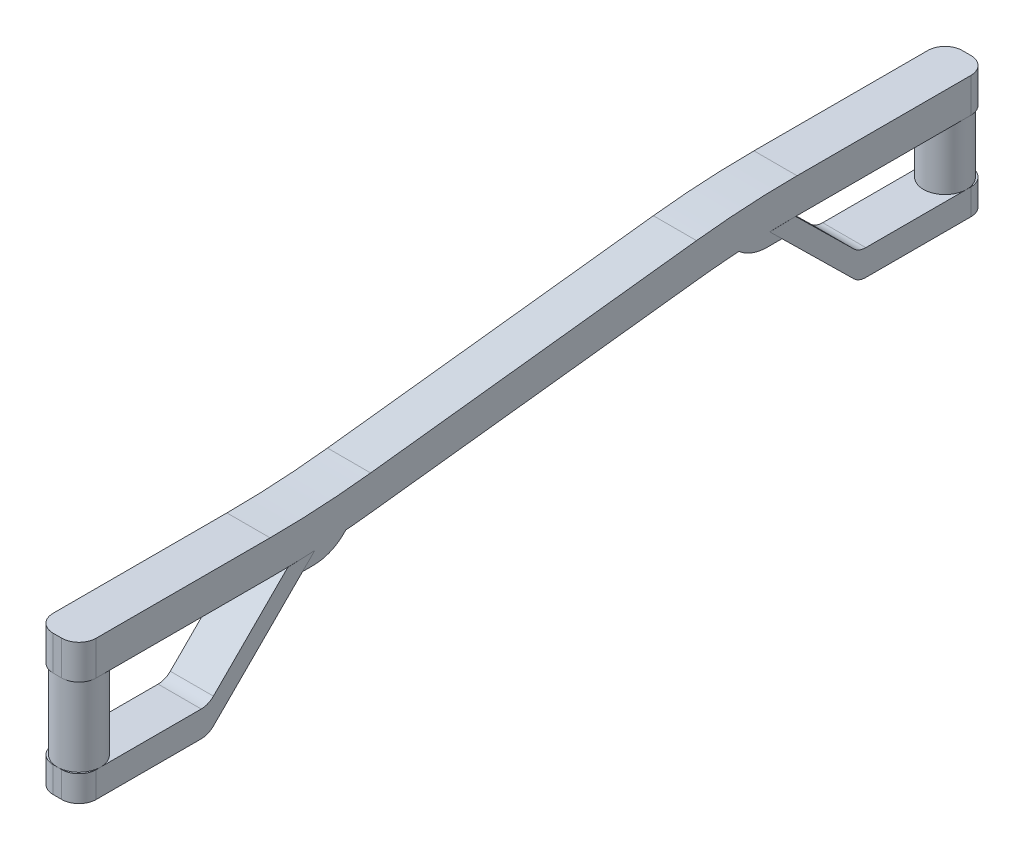
SolidWorks part; units mm, degrees
note: The reader was unsure of these and kept them because the rebuilt part matched: shared geometry of "Sketch1<3>", "Sketch1<4>", "Sketch4<4>".
other "End Rod cap 2"
other "End Rod Cap"
other "Long Connecting Rod"
material "PLA 100% Infill"
ref_plane "Front Plane" through (0, 0, 0) normal (0, 0, 1) x (1, 0, 0)
ref_plane "Top Plane" through (0, 0, 0) normal (0, 1, 0) x (1, 0, 0)
ref_plane "Right Plane" through (0, 0, 0) normal (1, 0, 0) x (0, 0, -1)
sketch "Sketch1" plane through (0, 0, 0) normal (0, 1, 0) x (1, 0, 0)
  line L1 (0, 0) -> (-5, 0)
  line L2 (0, 0) -> (0, -105.4)
  line L3 (0, -105.4) -> (-5, -105.4)
  line L4 (-5, 0) -> (-5, -105.4)
  circle A0 centre (-2.5, -2.5) radius 2.5
  circle A1 centre (-2.5, -102.9) radius 2.5
  dimension "D1" = 100.4
  dimension "D2" = 5
extrude "Boss-Extrude1" add sketch "Sketch1" along normal blind 4 contours L4 L3 L2 L1
extrude "Boss-Extrude2" add sketch "Sketch1<3>" against normal blind 15 contours A1
sketch "Sketch1<3>" plane through (0, 0, 0) normal (0, 1, 0) x (1, 0, 0) same geometry as "Sketch1"
extrude "Boss-Extrude3" add sketch "Sketch1<4>" against normal blind 7.2 contours A0
sketch "Sketch1<4>" plane through (0, 0, 0) normal (0, 1, 0) x (1, 0, 0) same geometry as "Sketch1"
fillet "Fillet1" radius 1 2 edges at (0, 2, 105.4) (-5, 2, 105.4)
ref_plane "Plane1" through (0, -17.2, 0) normal (0, -1, 0) x (-1, 0, 0)
sketch "Sketch2" plane through (0, -15, 0) normal (0, -1, 0) x (1, 0, 0)
  line L3 (-1.8333, 104.0547) -> (-1.8333, 101.7453)
  line L4 (-1.8333, 101.7453) -> (-3.8333, 102.9)
  line L6 (-3.8333, 102.9) -> (-1.8333, 104.0547)
  line L7 (-3.8333, 102.9) -> (-1.8333, 102.9) construction
  line L8 (-2.5, 105.4) -> (-2.5, 100.4) construction
  line L9 (-2.8333, 103.4774) -> (-1.8333, 101.7453) construction
  arc A0 (-5, 102.9) -> (0, 102.9) centre (-2.5, 102.9) ccw construction
  point P11 (-2.5, 102.9)
  dimension "D1" = 2
extrude "Cut-Extrude1" cut sketch "Sketch2" against normal blind 7
sketch "Sketch3" plane through (0, -7.2, 0) normal (0, -1, 0) x (-1, 0, 0)
  line L0 (3.1667, -1.3453) -> (3.1667, -3.6547)
  line L1 (3.1667, -3.6547) -> (1.1667, -2.5)
  line L2 (1.1667, -2.5) -> (3.1667, -1.3453)
  line L3 (1.1667, -2.5) -> (3.1667, -2.5) construction
  line L4 (2.5, 0) -> (2.5, -5) construction
  line L5 (2.1667, -1.9226) -> (3.1667, -3.6547) construction
  arc A1 (0, -2.5) -> (5, -2.5) centre (2.5, -2.5) ccw construction
  point P8 (2.5, -2.5)
  dimension "D1" = 2
extrude "Cut-Extrude2" cut sketch "Sketch3" against normal blind 7
sketch "Sketch4" plane through (-5, 0, 0) normal (-1, 0, 0) x (0, 0, 1)
  line L0 (105.4, -1.8) -> (105.4, -5.8)
  line L1 (105.4, -15) -> (105.4, 0) construction
  line L2 (105.4, -5.8) -> (77.4, -5.8)
  line L3 (77.4, -5.8) -> (28, 0)
  line L4 (2.5, 0) -> (102.9, 0) construction
  line L5 (105.4, -1.8) -> (77.4, -1.8)
  line L7 (77.4, -1.8) -> (77.4, -5.8) construction
  line L9 (0, 4) -> (104.4, 4) construction
  line L10 (28, 4) -> (28, 0)
  line L11 (28, 4) -> (105.4, 4)
  line L12 (105.4, 4) -> (105.4, -1.8)
  line L13 (28, 4) -> (77.4, -1.8)
  dimension "D1" = 4
  dimension "D2" = 28
  dimension "D3" = 5.8
  dimension "28" = 28
extrude "Boss-Extrude4" add sketch "Sketch4" against normal up to surface (5 mm away) up to face at (0, 1.3333, 52.3667)
extrude "Cut-Extrude3" cut sketch "Sketch4<4>" against normal up to surface (5 mm away)
sketch "Sketch4<4>" plane through (-5, 0, 0) normal (-1, 0, 0) x (0, 0, 1) same geometry as "Sketch4"
fillet "Fillet2" radius 100 4 edges at (-2.5, 4, 28) (-2.5, -1.8, 77.4) (-2.5, -5.8, 77.4) (-2.5, 0, 28)
sketch "Sketch5" plane through (0, 0, 0) normal (1, 0, 0) x (0, 0, -1)
  line L0 (-90.4, -15) -> (-81.2, -5.8)
  line L1 (-105.4, -15) -> (-90.4, -15)
  line L2 (-105.4, -15) -> (-105.4, -18)
  line L3 (-105.4, -18) -> (-90.4, -18)
  line L4 (-90.4, -15) -> (-90.4, -18) construction
  line L5 (-102.9, -5.8) -> (-83.2504, -5.8) construction
  line L6 (-90.4, -18) -> (-78.0655, -5.6655)
  line L7 (-5, -7.2) -> (0, -7.2) construction
  line L8 (0, -7.2) -> (-15, -7.2)
  line L9 (0, -7.2) -> (0, -10.2)
  line L10 (0, -10.2) -> (-15, -10.2)
  line L11 (-15, -7.2) -> (-15, -10.2) construction
  line L12 (-15, -7.2) -> (-22.3212, -0.0001)
  line L13 (-15, -10.2) -> (-25.3208, -0.0503)
  line L14 (0, -7.2) -> (0, 0) construction
  line L15 (-22.3212, -0.0001) -> (-25.3208, -0.0503)
  line L17 (-81.2, -5.8) -> (-78.0655, -5.6655)
  arc A0 (-83.2504, -5.8) -> (-71.5896, -5.1178) centre (-83.2504, 94.2) ccw construction
  arc A1 (-22.1496, 0) -> (-33.8104, -0.6822) centre (-22.1496, -100) ccw construction
  dimension "D1" = 45
  dimension "D3" = 3
  dimension "D4" = 15
extrude "Boss-Extrude6" add sketch "Sketch5" against normal up to surface (5 mm away) separate body up to face at (-5, -1.1857, 52.7)
sketch "Sketch6" plane through (0, 0, 0) normal (1, 0, 0) x (0, 0, -1)
  line L0 (-78.0655, -5.6655) -> (-79.4797, -7.0797)
  line L1 (-52.7, 1.1) -> (-52.7, -2.9) construction
  line L2 (-33.8104, 3.3178) -> (-71.5896, -1.1178) construction
  line L3 (-71.5896, -5.1178) -> (-33.8104, -0.6822) construction
  line L5 (-28.8948, -0.2277) -> (-28.8948, -1.4526)
  line L7 (-90.4, -18) -> (-78.0655, -5.6655) construction
  line L8 (-79.4797, -7.0797) -> (-74.4797, -7.0797)
  line L9 (-74.4797, -7.0797) -> (-74.4797, -5.4146)
  line L12 (-78.0655, -5.6655) -> (-74.4797, -5.4146)
  line L16 (-28.8948, -1.4526) -> (-23.8948, -1.4526)
  line L17 (-25.3208, -0.0503) -> (-15, -10.2) construction
  line L18 (-23.8948, -1.4526) -> (-25.3208, -0.0503)
  arc A0 (-22.1496, 0) -> (-33.8104, -0.6822) centre (-22.1496, -100) ccw construction
  arc A1 (-83.2504, -5.8) -> (-71.5896, -5.1178) centre (-83.2504, 94.2) ccw construction
  arc A3 (-25.3208, -0.0503) -> (-28.8948, -0.2277) centre (-22.1496, -100) ccw
  dimension "D1" = 2
  dimension "D3" = 5
  dimension "D4" = 5
extrude "Boss-Extrude7" add sketch "Sketch6" against normal up to surface (5 mm away) up to face at (-5, -1.1857, 52.7)
fillet "Fillet3" radius 5 2 edges at (-2.5, -7.0797, 74.4797) (-2.5, -1.4526, 28.8948)
fillet "Fillet4" radius 2 4 edges at (-2.5, -10.2, 15) (0, -8.7, 0) (-5, -8.7, 0) (-2.5, -7.2, 15)
fillet "Fillet5" radius 2 4 edges at (-5, 2, 0) (0, 2, 0) (-5, -3.8, 105.4) (0, -3.8, 105.4)
fillet "Fillet6" radius 2 4 edges at (-2.5, -15, 90.4) (-2.5, -18, 90.4) (-5, -16.5, 105.4) (0, -16.5, 105.4)
